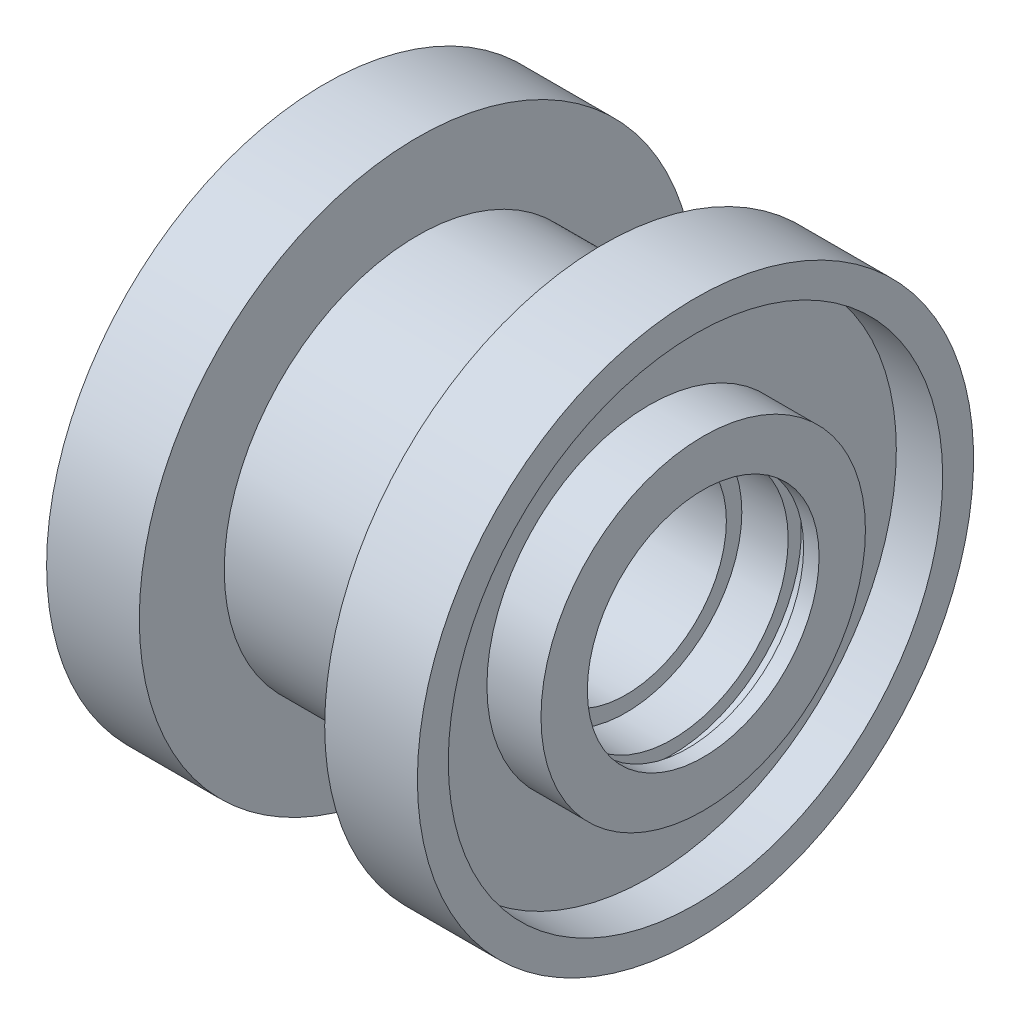
SolidWorks part; units mm, degrees
material "PS HI"
ref_plane "Płaszczyzna przednia" through (0, 0, 0) normal (0, 0, 1) x (1, 0, 0)
ref_plane "Płaszczyzna górna" through (0, 0, 0) normal (0, 1, 0) x (1, 0, 0)
ref_plane "Płaszczyzna prawa" through (0, 0, 0) normal (1, 0, 0) x (0, 0, -1)
sketch "Szkic1" plane through (0, 0, 0) normal (0, 0, 1) x (1, 0, 0)
  line L0 (-30.8375, 0) -> (30.8375, 0) construction
  line L1 (0, -37.8176) -> (0, 37.8176) construction
  line L2 (-6, 12.5) -> (6, 12.5)
  line L3 (6, 12.5) -> (6, 18)
  line L4 (6, 18) -> (12, 18)
  line L5 (12, 18) -> (12, 16)
  line L6 (12, 16) -> (9, 16)
  line L7 (9, 16) -> (9, 10.5)
  line L10 (-12, 16) -> (-9, 16)
  line L11 (-12, 18) -> (-12, 16)
  line L12 (-6, 18) -> (-12, 18)
  line L13 (-6, 12.5) -> (-6, 18)
  line L15 (12.5, 7.5) -> (12.5, 10.5)
  line L16 (12.5, 10.5) -> (9, 10.5)
  line L18 (-9, 16) -> (-9, 10.5)
  line L20 (-12.5, 7.5) -> (-12.5, 10.5)
  line L21 (-12.5, 10.5) -> (-9, 10.5)
  line L22 (12.5, 7.5) -> (11.5, 7.5)
  line L23 (7.5, 7.5) -> (7.5, 6.5)
  line L24 (7.5, 6.5) -> (-7.5, 6.5)
  line L25 (-7.5, 7.5) -> (-10.5, 7.5)
  line L26 (-7.5, 7.5) -> (-7.5, 6.5)
  line L27 (11.5, 7.5) -> (11.5, 8.35)
  line L28 (11.5, 8.35) -> (10.5, 8.35)
  line L29 (10.5, 8.35) -> (10.5, 7.5)
  line L30 (10.5, 7.5) -> (7.5, 7.5)
  line L31 (-11.5, 7.5) -> (-11.5, 8.35)
  line L32 (-10.5, 8.35) -> (-10.5, 7.5)
  line L33 (-11.5, 8.35) -> (-10.5, 8.35)
  line L34 (-11.5, 7.5) -> (-12.5, 7.5)
  point P1 (12, 17)
  point P7 (0, 0)
  point P14 (0, 7.5)
  point P15 (7.5, 7.5)
  point P21 (0, 12.5)
  point P23 (12.5, 9)
  point P32 (0, 6.5)
  dimension "D1" = 15
  dimension "D2" = 25
  dimension "D3" = 32
  dimension "D4" = 36
  dimension "D5" = 3
  dimension "D6" = 6
  dimension "D7" = 12
  dimension "D8" = 21
  dimension "D9" = 3.5
  dimension "D10" = 25
  dimension "D11" = 5
  dimension "D12" = 13
  dimension "D13" = 0.85
  dimension "D14" = 1
  dimension "D15" = 3
revolve "Obrót1" add sketch "Szkic1" angle 360 about L0
sketch "Szkic2" plane through (-12, 0, 0) normal (-1, 0, 0) x (0, 0, 1)
  line L0 (0, 18) -> (0, 16) construction
  circle A0 centre (0, 17) radius 0.5
  dimension "D1" = 1
extrude "Wytnij-wyciągnięcie1" cut sketch "Szkic2" against normal blind 1
